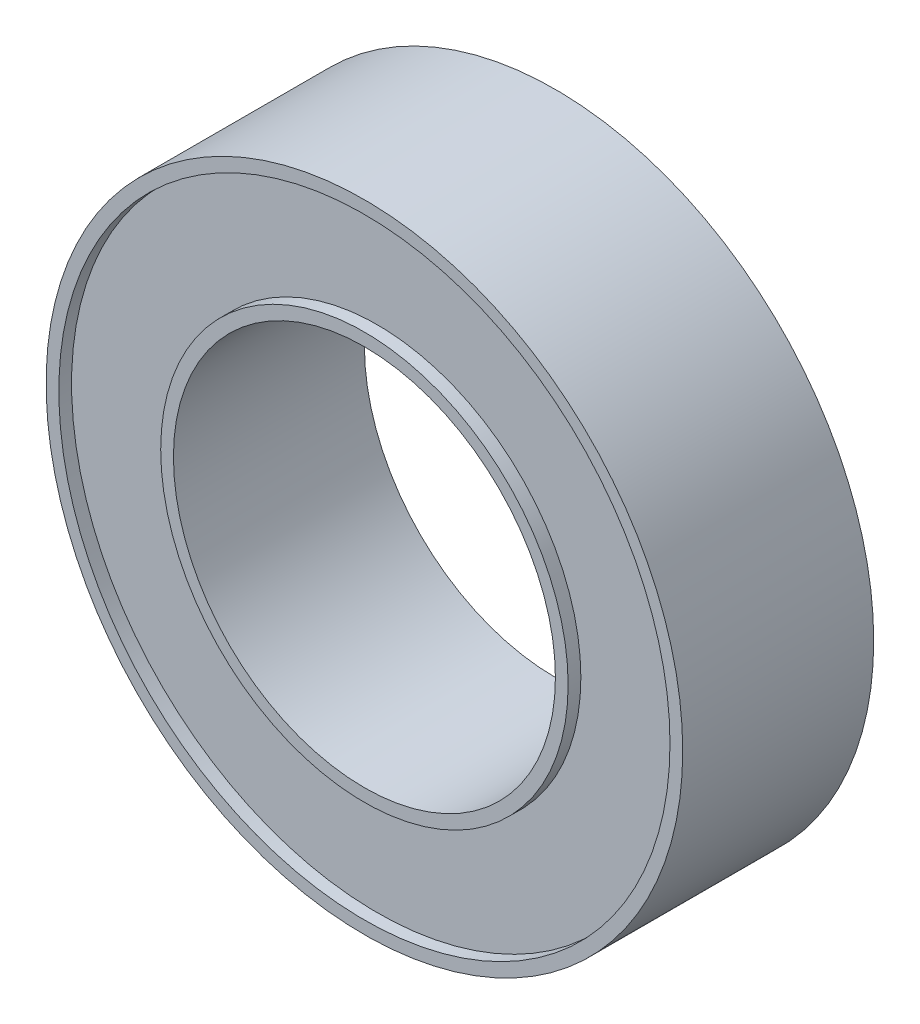
SolidWorks part; units mm, degrees
ref_plane "前视基准面" through (0, 0, 0) normal (0, 0, 1) x (1, 0, 0)
ref_plane "上视基准面" through (0, 0, 0) normal (0, 1, 0) x (1, 0, 0)
ref_plane "右视基准面" through (0, 0, 0) normal (1, 0, 0) x (0, 0, -1)
sketch "草图1" plane through (0, 0, 0) normal (0, 0, 1) x (1, 0, 0)
  circle A0 centre (0, 0) radius 3
  circle A1 centre (0, 0) radius 5
  dimension "D1" = 6
  dimension "D2" = 10
extrude "凸台-拉伸1" add sketch "草图1" along normal blind 1.5 and the other way blind 1.5
sketch "草图2" plane through (0, 0, 1.5) normal (0, 0, 1) x (1, 0, 0)
  circle A0 centre (0, 0) radius 4.8
  circle A1 centre (0, 0) radius 3.2
  circle A2 centre (0, 0) radius 5 construction
  circle A3 centre (0, 0) radius 3 construction
  dimension "D1" = 0.2
  dimension "D2" = 0.2
extrude "切除-拉伸1" cut sketch "草图2" against normal blind 0.2
mirror "镜向1" about plane through (0, 0, 0) normal (0, 0, 1) of "切除-拉伸1"
